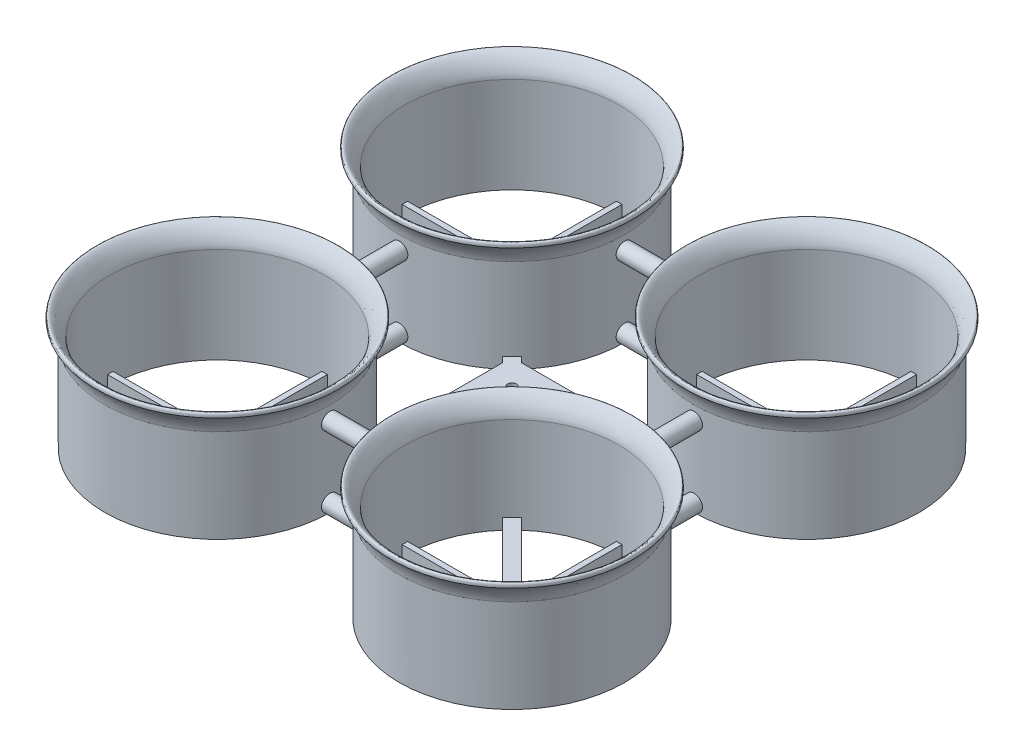
SolidWorks part; units mm, degrees
note: '?' marks a value the reader was unsure of.
ref_plane "Front Plane" through (0, 0, 0) normal (0, 0, 1) x (1, 0, 0)
ref_plane "Top Plane" through (0, 0, 0) normal (0, 1, 0) x (1, 0, 0)
ref_plane "Right Plane" through (0, 0, 0) normal (1, 0, 0) x (0, 0, -1)
ref_axis "X Axis" through (-102.512, 0, 0) along (1, 0, 0)?
ref_axis "Y Axis" through (0, 0, -107.1526) along (0, 0, 1)?
ref_axis "Z Axis" through (0, 27.7441, 0) along (0, -1, 0)?
sketch "Sketch1" plane through (0, 0, 0) normal (0, 1, 0) x (1, 0, 0)
  line L0 (-53.7401, 53.7401) -> (53.7401, -53.7401) construction
  line L2 (-50.5581, 56.9221) -> (-56.9221, 50.5581) construction
  line L12 (-102.512, 0) -> (116.8771, 0) construction
  line L13 (53.7401, 53.7401) -> (-53.7401, -53.7401) construction
  line L21 (-56.9221, 56.9221) -> (-50.5581, 50.5581) construction
  line L22 (-53.7401, 46.7401) -> (-53.7401, 17.6401) construction
  line L23 (-52.7401, 46.8119) -> (-52.7401, 14.6529)
  line L25 (-54.7401, 46.8119) -> (-54.7401, 14.6529)
  line L27 (-54.7401, 37.4136) -> (-52.7401, 37.4136) construction
  line L29 (-60.6683, 52.7401) -> (-92.8273, 52.7401)
  line L30 (-60.6683, 54.7401) -> (-92.8273, 54.7401)
  line L31 (-54.7401, 60.6683) -> (-54.7401, 92.8273)
  line L32 (-52.7401, 60.6683) -> (-52.7401, 92.8273)
  line L33 (-46.8119, 54.7401) -> (-14.6529, 54.7401)
  line L34 (-46.8119, 52.7401) -> (-14.6529, 52.7401)
  circle A0 centre (0, 0) radius 76 construction
  circle A2 centre (-53.7401, 53.7401) radius 4.5 construction
  circle A3 centre (-56.9221, 56.9221) radius 1.05
  circle A4 centre (-50.5581, 56.9221) radius 1.05
  circle A5 centre (-50.5581, 50.5581) radius 1.05
  circle A6 centre (-56.9221, 50.5581) radius 1.05
  circle A22 centre (-53.7401, 53.7401) radius 2.5
  arc A33 (-54.7401, 60.6683) -> (-60.6683, 54.7401) centre (-53.7401, 53.7401) ccw
  arc A34 (-92.8273, 52.7401) -> (-54.7401, 14.6529) centre (-53.7401, 53.7401) ccw
  circle A35 centre (-53.7401, 53.7401) radius 41.1
  circle A36 centre (-53.7401, 53.7401) radius 39.1 construction
  arc A37 (-54.7401, 92.8273) -> (-92.8273, 54.7401) centre (-53.7401, 53.7401) ccw
  arc A38 (-60.6683, 52.7401) -> (-54.7401, 46.8119) centre (-53.7401, 53.7401) ccw
  arc A39 (-46.8119, 54.7401) -> (-52.7401, 60.6683) centre (-53.7401, 53.7401) ccw
  arc A40 (-52.7401, 46.8119) -> (-46.8119, 52.7401) centre (-53.7401, 53.7401) ccw
  arc A41 (-14.6529, 54.7401) -> (-52.7401, 92.8273) centre (-53.7401, 53.7401) ccw
  arc A42 (-52.7401, 14.6529) -> (-14.6529, 52.7401) centre (-53.7401, 53.7401) ccw
  point P4 (0, 0)
  point P7 (0, 0)
  point P16 (-53.7401, 53.7401)
  point P32 (-53.7401, 37.4136)
  point P49 (-53.7401, 53.7401)
  point P50 (-53.7401, 53.7401)
  dimension "D1" = 152
  dimension "D4" = 9
  dimension "D5" = 2.1
  dimension "D6" = 5
  dimension "D3" = 14
  dimension "D7" = 78.2
  dimension "D2" = 45
  dimension "D9" = 2
  dimension "D8" = 2
  dimension "D10" = 4
ref_plane "45 Deg" through (0, 0, 0) normal (0.7071, 0, 0.7071) x (0, -1, 0)
extrude "Boss-Extrude3" add sketch "Sketch1" along normal blind 4
ref_axis "Axis1" through (-53.7401, 40.4764, -53.7401) along (0, -1, 0)
ref_plane "Plane2" through (0, 0, -53.7401) normal (0, 0, 1) x (1, 0, 0)
sketch "Sketch6" plane through (0, 0, -53.7401) normal (0, 0, 1) x (1, 0, 0)
  line L0 (-94.8401, 4) -> (-94.8401, 34)
  line L1 (-12.6401, 4) -> (-94.8401, 4) construction
  line L2 (-92.8401, 4) -> (-92.8401, 34.925)
  line L3 (-54.7401, 4) -> (-92.8273, 4) construction
  line L4 (-94.8401, 4) -> (-92.8401, 4)
  line L5 (-97.9401, 40.5) -> (-97.9401, 26.67) construction
  spline S0 degree 2 poles (-94.8401, 34) (-95.3995, 37.7213) (-97.9401, 40.5) knots 0 0 0 1 1 1
  spline S1 degree 3 poles (-97.9401, 40.5) (-98.333, 44.8536) (-92.9834, 38.4176) (-92.8401, 34.925) knots 0 0 0 0 1 1 1 1
  point P12 (0, 0)
  point P14 (0, 0)
  point P15 (0, 0)
  point P16 (-95.885, 37.465)
  dimension "D4" = 6.5
  dimension "D1" = 30
  dimension "D2" = 2
  dimension "D3" = 3.1
revolve "Revolve1" add sketch "Sketch6" angle 360 about axis through (-53.7401, 40.4764, -53.7401) along (0, -1, 0)
pattern_circular "CirPattern1" count 4 over 360 about axis through (0, 27.7441, 0) along (0, -1, 0) of bodies 118
sketch "Sketch8" plane through (0, 0, 0) normal (0, 0, 1) x (1, 0, 0)
  line L0 (-53.7401, 40.4764) -> (-53.7401, -26.5975) construction
  line L1 (-102.512, 0) -> (116.8771, 0) construction
  line L2 (0, -49.9102) -> (0, 49.9102) construction
  circle A0 centre (-53.7401, 3.0962) radius 3
  circle A1 centre (-53.7401, 29) radius 3
  circle A2 centre (53.7401, 3.0962) radius 3
  circle A3 centre (53.7401, 29) radius 3
  dimension "D1" = 6
  dimension "D2" = 29
extrude "Boss-Extrude6" add sketch "Sketch8" against normal up to vertex and the other way up to vertex
sketch "Sketch10" plane through (0, 0, 0) normal (1, 0, 0) x (0, 0, -1)
  circle A0 centre (-53.7401, 3.0962) radius 3
  circle A1 centre (-53.7401, 29) radius 3
  circle A2 centre (53.7401, 3.0962) radius 3
  circle A3 centre (53.7401, 29) radius 3
  dimension "D1" = 6
sketch "Sketch9" plane through (0, 0, 0) normal (0, 1, 0) x (1, 0, 0)
  line L0 (-53.7401, 53.7401) -> (53.7401, -53.7401) construction
  line L1 (53.7401, 53.7401) -> (-53.7401, -53.7401) construction
  line L2 (-50.8846, -47.349) -> (-24.5, -20.9645)
  line L3 (50.8846, 47.349) -> (24.5, 20.9645)
  line L4 (-47.349, -50.8846) -> (-50.8846, -47.349)
  line L5 (47.349, 50.8846) -> (50.8846, 47.349)
  line L6 (-47.349, 50.8846) -> (-20.9645, 24.5)
  line L7 (50.8846, -47.349) -> (47.349, -50.8846)
  line L8 (47.349, -50.8846) -> (20.9645, -24.5)
  line L9 (-50.8846, 47.349) -> (-47.349, 50.8846)
  line L10 (20.9645, 24.5) -> (47.349, 50.8846)
  line L11 (24.5, -20.9645) -> (50.8846, -47.349)
  line L12 (-24.5, 20.9645) -> (-50.8846, 47.349)
  line L13 (-20.9645, -24.5) -> (-47.349, -50.8846)
  line L14 (-102.512, 0) -> (116.8771, 0) construction
  line L15 (-20.9645, 24.5) -> (20.9645, 24.5)
  line L16 (-24.5, 20.9645) -> (-24.5, -20.9645)
  line L17 (-20.9645, -24.5) -> (20.9645, -24.5)
  line L18 (24.5, 20.9645) -> (24.5, -20.9645)
  arc A0 (-46.8119, -52.7401) -> (-52.7401, -46.8119) centre (-53.7401, -53.7401) ccw construction
  arc A1 (46.8119, 52.7401) -> (52.7401, 46.8119) centre (53.7401, 53.7401) ccw construction
  circle A2 centre (-15.25, 15.25) radius 1.6
  circle A3 centre (15.25, 15.25) radius 1.6
  circle A4 centre (15.25, -15.25) radius 1.6
  circle A5 centre (-15.25, -15.25) radius 1.6
  point P18 (49.1168, 49.1168)
  point P25 (0, 0)
  point P39 (0, 0)
  point P42 (0, 0)
  point P45 (0, 0)
  point P48 (0, 0)
  dimension "D4" = 3.2
  dimension "D1" = 5
  dimension "D5" = 15.25
  dimension "D2" = 2
  dimension "D6" = 4
extrude "Boss-Extrude7" add sketch "Sketch9" along normal blind 4
extrude "Boss-Extrude8" add sketch "Sketch10" along normal up to vertex and the other way up to vertex
equation "\"wingspan\"= 152mm"
equation "\"D1@Sketch1\"=\"wingspan\""
equation "\"Motor hub thickenss\"= 4mm"
equation "\"Arm thickness\"= 8mm"
equation "\"Prop Dia\"= 76.2mm"
equation "\"D1@Boss-Extrude3\"=\"Motor hub thickenss\""
equation "\"D7@Sketch1\"=\"Prop Dia\"+2"
equation "\"D1@Boss-Extrude7\"=\"Motor hub thickenss\""
